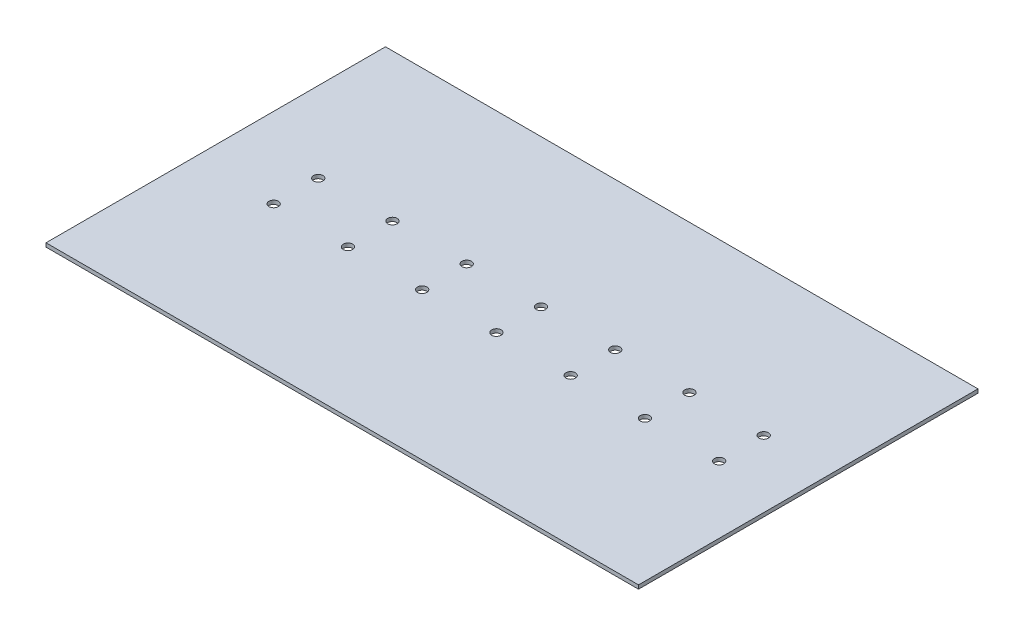
SolidWorks part; units mm, degrees
ref_plane "Front Plane" through (0, 0, 0) normal (0, 0, 1) x (1, 0, 0)
ref_plane "Top Plane" through (0, 0, 0) normal (0, 1, 0) x (1, 0, 0)
ref_plane "Right Plane" through (0, 0, 0) normal (1, 0, 0) x (0, 0, -1)
sketch "Sketch1" plane through (0, 0, 0) normal (0, 1, 0) x (1, 0, 0)
  line L1 (0, 0) -> (399, 0)
  line L2 (0, 0) -> (0, -228.6)
  line L3 (0, -228.6) -> (399, -228.6)
  line L4 (399, 0) -> (399, -228.6)
  dimension "D1" = 399
  dimension "D2" = 228.6
extrude "Base" add sketch "Sketch1" against normal blind 2.54
sketch "Sketch9" plane through (0, 0, 0) normal (0, 1, 0) x (1, 0, 0)
  line L0 (0, -114.3) -> (399, -114.3) construction
  line L1 (0, 0) -> (0, -228.6) construction
  line L2 (399, -228.6) -> (399, 0) construction
  point P6 (304, -129.3)
  point P8 (304, -99.3)
  point P9 (254, -129.3)
  point P10 (254, -99.3)
  point P11 (204, -129.3)
  point P12 (354, -129.3)
  point P13 (354, -99.3)
  point P14 (204, -99.3)
  point P15 (154, -129.3)
  point P16 (154, -99.3)
  point P17 (104, -129.3)
  point P18 (104, -99.3)
  point P19 (54, -129.3)
  point P20 (54, -99.3)
  dimension "D2" = 45
  dimension "D3" = 15
  dimension "D4" = 50
  dimension "D1" = 7
hole_wizard "Hole for #10 Blind Fasteners (B,BS)1" positions "Sketch10" profile "Sketch11" hole size "#10-32" standard "PEM® Inch" end condition through all
sketch "Sketch10" plane through (0, 0, 0) normal (0, 1, 0) x (1, 0, 0)
  point P0 (354, -129.3)
  point P3 (304, -129.3)
  point P6 (254, -129.3)
  point P9 (204, -129.3)
  point P12 (154, -129.3)
  point P15 (104, -129.3)
  point P18 (54, -129.3)
  point P21 (54, -99.3)
  point P24 (104, -99.3)
  point P27 (154, -99.3)
  point P30 (204, -99.3)
  point P33 (254, -99.3)
  point P36 (304, -99.3)
  point P39 (354, -99.3)
sketch "Sketch11" plane through (354, 0, 129.3) normal (1, 0, 0) x (0, 0, 1)
  line L0 (0, 0) -> (0, 2.54)
  line L1 (0, 2.54) -> (3.175, 2.54)
  line L2 (3.175, 2.54) -> (3.175, 0)
  line L5 (3.175, 0) -> (0, 0)
  line L11 (0, -6.35) -> (0, 107.95) construction
  dimension "Thru Hole Dia." = 6.35
  dimension "Thru Hole Depth" = 2.54
